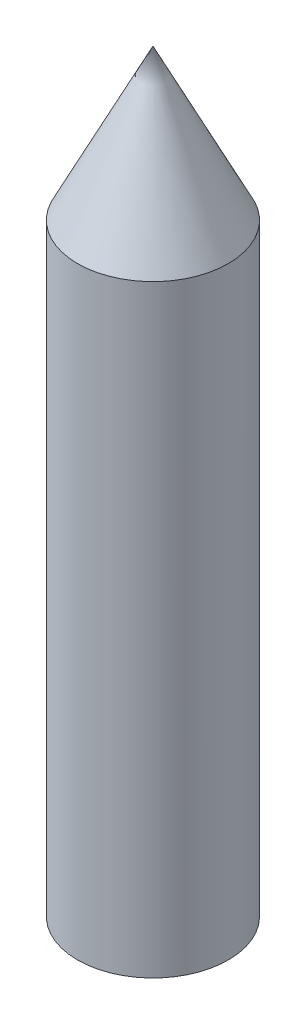
SolidWorks part; units mm, degrees
ref_plane "Front Plane" through (0, 0, 0) normal (0, 0, 1) x (1, 0, 0)
ref_plane "Top Plane" through (0, 0, 0) normal (0, 1, 0) x (1, 0, 0)
ref_plane "Right Plane" through (0, 0, 0) normal (1, 0, 0) x (0, 0, -1)
sketch "Sketch1" plane through (0, 0, 0) normal (0, 1, 0) x (1, 0, 0)
  circle A0 centre (0, 0) radius 6.35
  dimension "D1" = 12.7
extrude "Boss-Extrude1" add sketch "Sketch1" along normal blind 50.8
sketch "Sketch4" plane through (0, 0, 0) normal (0, 0, 1) x (1, 0, 0)
  line L0 (6.35, 50.8) -> (-6.35, 50.8)
  line L1 (6.35, 50.8) -> (-6.35, 50.8) construction
  line L2 (-6.35, 0) -> (-6.35, 50.8)
  line L3 (6.35, 50.8) -> (6.35, 0)
  line L4 (6.35, 50.8) -> (6.35, 0) construction
  line L5 (-6.35, 0) -> (-6.35, 50.8) construction
  line L6 (0, 50.8) -> (0, 63.5)
  line L7 (0, 63.5) -> (6.35, 50.8)
  line L8 (6.35, 50.8) -> (0, 50.8)
  dimension "D1" = 12.7
revolve "Revolve2" add sketch "Sketch4" angle 360 about L6
ref_axis "Axis1" through (0, 66.675, 0) along (0, -1, 0)
